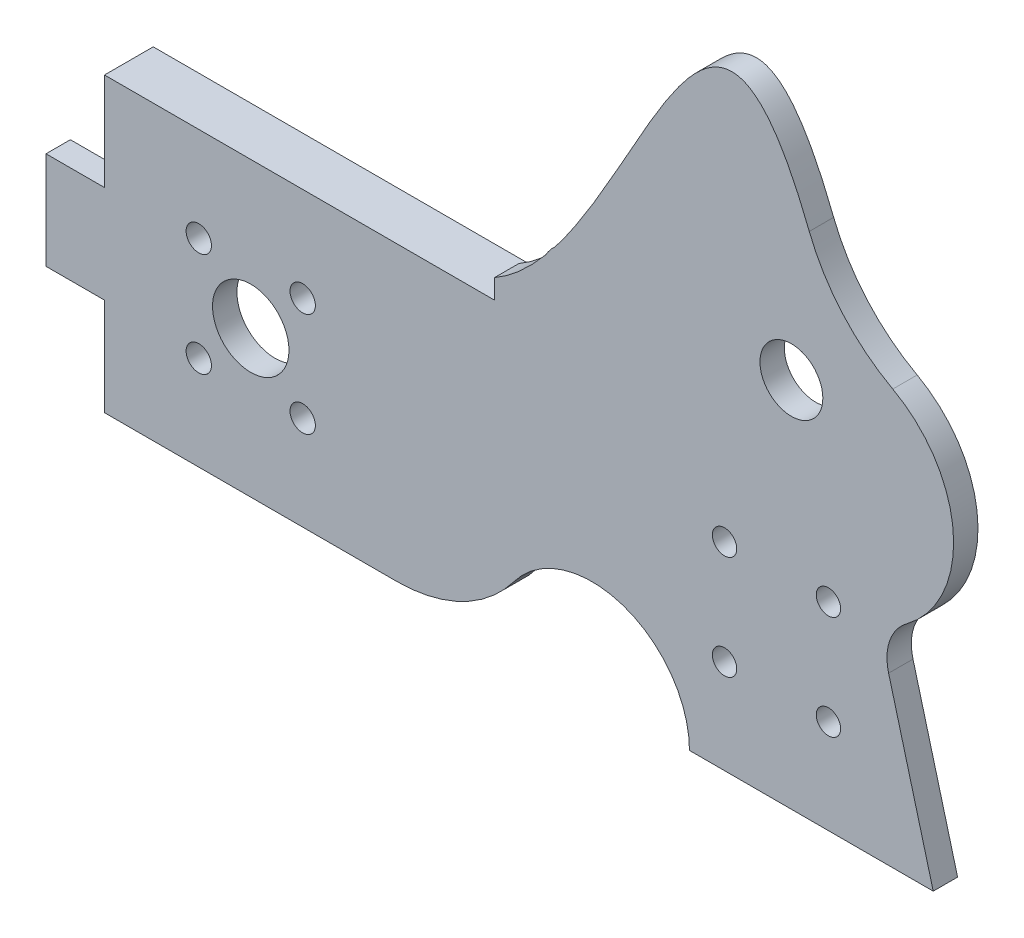
SolidWorks part; units mm, degrees
ref_plane "Front Plane" through (0, 0, 0) normal (0, 0, 1) x (1, 0, 0)
ref_plane "Top Plane" through (0, 0, 0) normal (0, 1, 0) x (1, 0, 0)
ref_plane "Right Plane" through (0, 0, 0) normal (1, 0, 0) x (0, 0, -1)
sketch "Sketch1" plane through (0, 0, 0) normal (0, 0, 1) x (1, 0, 0)
  line L0 (0, 0) -> (107.95, 0)
  line L3 (0, 38.1) -> (0, 25.4)
  line L4 (95.3675, 55.88) -> (0, 38.1)
  line L5 (0, 19.05) -> (100.2273, 19.05) construction
  line L6 (19.05, 19.05) -> (19.05, 28.62) construction
  line L7 (19.05, 19.05) -> (25.817, 25.817) construction
  line L8 (107.95, 0) -> (100.9363, 26.1756)
  line L10 (0, 12.7) -> (0, 0)
  line L11 (0, 25.4) -> (-7.62, 25.4)
  line L13 (0, 12.7) -> (-7.62, 12.7)
  line L14 (-7.62, 25.4) -> (-7.62, 12.7)
  line L15 (100.9363, 26.1756) -> (100.8688, 26.4276)
  arc A0 (100.8688, 26.4276) -> (95.3675, 55.88) centre (95.3675, 40.64) ccw
  circle A1 centre (95.3675, 40.64) radius 4.0957 construction
  circle A2 centre (19.05, 19.05) radius 9.57 construction
  circle A3 centre (25.817, 25.817) radius 1.651
  circle A4 centre (25.817, 12.283) radius 1.651
  circle A5 centre (12.283, 12.283) radius 1.651
  circle A6 centre (12.283, 25.817) radius 1.651
  point P26 (19.05, 19.05)
  dimension "D1" = 8.1915
  dimension "D5" = 15.24
  dimension "D4" = 19.14
  dimension "D7" = 3.302
  dimension "D11" = 97.0107
  dimension "D2" = 38.1
  dimension "D3" = 40.64
  dimension "D6" = 107.95
  dimension "D8" = 45
  dimension "D9" = 4
  dimension "D10" = 19.05
  dimension "D12" = 75
  dimension "D14" = 12.7
  dimension "D15" = 12.7
  dimension "D16" = 7.62
extrude "Boss-Extrude1" add sketch "Sketch1" along normal blind 3.175
sketch "Sketch2" plane through (0, 0, 3.175) normal (0, 0, 1) x (1, 0, 0)
  circle A0 centre (95.3675, 40.64) radius 38.1 construction
sketch "Sketch6" plane through (0, 0, 3.175) normal (0, 0, 1) x (1, 0, 0)
  line L0 (0, 0) -> (107.95, 0) construction
  line L1 (50.8, 0) -> (76.2, 0)
  arc A0 (76.2, 0) -> (50.8, 0) centre (63.5, 0) ccw
  dimension "D1" = 25.4
  dimension "D2" = 31.75
extrude "Cut-Extrude2" cut sketch "Sketch6" against normal blind 6.35
sketch "Sketch7" plane through (0, 0, 3.175) normal (0, 0, 1) x (1, 0, 0)
  line L0 (12.283, 25.817) -> (25.817, 12.283) construction
  line L1 (12.283, 12.283) -> (25.817, 25.817) construction
  line L2 (12.283, 25.817) -> (78.4839, 25.817) construction
  line L3 (11.7326, 12.283) -> (12.283, 12.283) construction
  circle A0 centre (19.05, 19.05) radius 4.9784
  circle A4 centre (80.7666, 12.283) radius 1.5875
  circle A5 centre (94.2997, 12.283) radius 1.5875
  circle A6 centre (80.7666, 25.817) radius 1.5875
  circle A7 centre (94.2997, 25.817) radius 1.5875
  dimension "D1" = 9.9568
  dimension "D2" = 3.175
  dimension "D3" = 13.5331
extrude "Cut-Extrude3" cut sketch "Sketch7" against normal through all
fillet "Fillet1" radius 6.35 1 edges at (100.8688, 26.4276, 1.5875)
sketch "Sketch8" plane through (0, 0, 3.175) normal (0, 0, 1) x (1, 0, 0)
  line L1 (0, 38.1) -> (50.8, 38.1)
  line L2 (0, 38.1) -> (0, 50.8)
  line L3 (0, 50.8) -> (50.8, 50.8)
  line L4 (50.8, 38.1) -> (50.8, 50.8)
  dimension "D1" = 50.8
  dimension "D2" = 12.7
extrude "Cut-Extrude4" cut sketch "Sketch8" against normal blind 50.8
sketch "Sketch9" plane through (0, 0, 3.175) normal (0, 0, 1) x (1, 0, 0)
  line L3 (50.8, 40.64) -> (57.15, 40.64)
  line L5 (57.15, 40.64) -> (50.8, 40.64)
  line L6 (57.15, 40.64) -> (57.15, 50.8)
  line L7 (57.15, 50.8) -> (50.8, 50.8)
  line L8 (50.8, 40.64) -> (50.8, 50.8)
  line L9 (0, 38.1) -> (50.8, 38.1) construction
  line M8 (50.8, 47.571) -> (50.8, 38.1)
  line M21 (95.3675, 55.88) -> (50.8, 47.571)
  dimension "D1" = 10.16
  dimension "D2" = 2.54
  dimension "D3" = 6.35
extrude "Cut-Extrude5" cut sketch "Sketch9" against normal blind 19.304 contours L3 L6 M21 M8 region at (54.0583, 44.4092, 3.175)
fillet "Fillet6" radius 6.35 1 edges at (57.15, 40.64, 1.5875)
fillet "Fillet7" radius 6.35 1 edges at (57.15, 48.7549, 1.5875)
fillet "Fillet8" radius 19.05 1 edges at (50.8, 0, 1.5875)
sketch "Sketch12" plane through (0, 0, 3.175) normal (0, 0, 1) x (1, 0, 0)
  line L0 (107.95, 0) -> (146.812, 0) construction
  line L1 (8.0257, 45.4128) -> (80.6683, 75.7903) construction
  line L2 (95.3675, 40.64) -> (80.6683, 75.7903) construction
  line L3 (80.6683, 75.7903) -> (79.4434, 78.7195) construction
  line L4 (50.8, 40.64) -> (85.0271, 40.64)
  line L5 (85.0271, 40.64) -> (95.3675, 55.88)
  arc A0 (61.8128, 49.6242) -> (56.8883, 45.1859) centre (62.9766, 43.3817) ccw construction
  circle A1 centre (19.05, 19.05) radius 28.575 construction
  circle A2 centre (95.3675, 40.64) radius 38.1 construction
  circle A3 centre (80.6683, 75.7903) radius 3.175 construction
  spline S0 degree 3 poles (50.8, 40.64) (70.7778, 52.1788) (78.5943, 111.5434) (95.3675, 55.88) knots 0 0 0 0 1 1 1 1
  dimension "D2" = 6.35
  dimension "D1" = 38.862
extrude "Boss-Extrude2" add sketch "Sketch12" against normal blind 3.175
fillet "Fillet9" radius 24.13 1 edges at (95.3675, 55.88, 1.5875)
sketch "Sketch13" plane through (0, 0, 0) normal (0, 0, -1) x (-1, 0, 0)
  line L0 (0, 38.1) -> (0, 25.4) construction
  line L1 (-50.8, 38.1) -> (0, 38.1)
  line L2 (-50.8, 38.1) -> (-50.8, 28.4023)
  line L3 (-50.8, 28.4023) -> (0, 28.4023)
  line L4 (0, 38.1) -> (0, 28.4023)
  line L5 (0, 12.7) -> (0, 0) construction
  line L6 (0, 8.5046) -> (-38.1, 8.5046)
  line L7 (0, 8.5046) -> (0, 0)
  line L8 (0, 0) -> (-38.1, 0)
  line L9 (-38.1, 8.5046) -> (-38.1, 0)
extrude "Boss-Extrude3" add sketch "Sketch13" along normal blind 3.175
sketch "Sketch16" plane through (0, 0, 3.175) normal (0, 0, 1) x (1, 0, 0)
  circle A0 centre (89.4737, 48.423) radius 4.0958
  circle A1 centre (94.2997, 25.817) radius 1.5875 construction
  point P2 (78.577, 53.3463)
  point P3 (83.1904, 53.1478)
  dimension "D1" = 22.606
  dimension "D2" = 4.826
extrude "Cut-Extrude8" cut sketch "Sketch16" against normal through all
